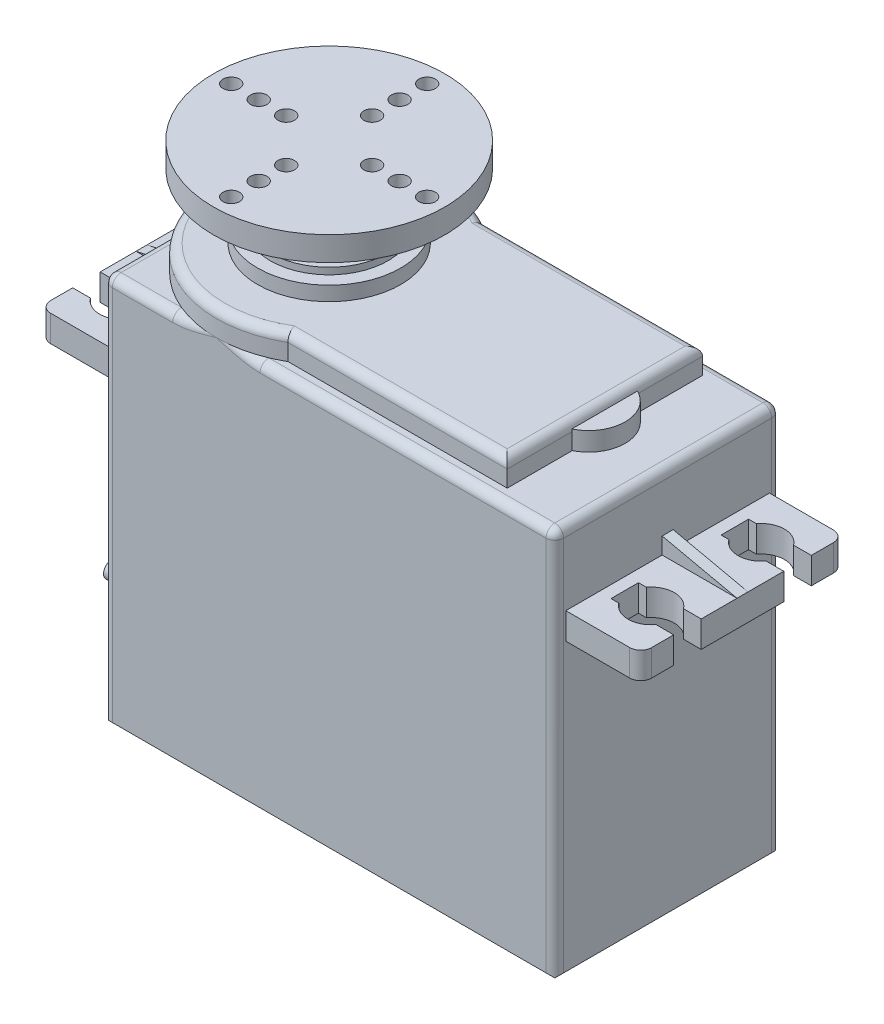
SolidWorks part; units mm, degrees
ref_plane "Front Plane" through (0, 0, 0) normal (0, 0, 1) x (1, 0, 0)
ref_plane "Top Plane" through (0, 0, 0) normal (0, 1, 0) x (1, 0, 0)
ref_plane "Right Plane" through (0, 0, 0) normal (1, 0, 0) x (0, 0, -1)
sketch "Sketch1" plane through (0, 0, 0) normal (0, 1, 0) x (1, 0, 0)
  line L1 (-20.5, 10.25) -> (20.5, 10.25)
  line L2 (-20.5, 10.25) -> (-20.5, -10.25)
  line L3 (-20.5, -10.25) -> (20.5, -10.25)
  line L4 (20.5, 10.25) -> (20.5, -10.25)
  line L5 (-20.5, 10.25) -> (20.5, -10.25) construction
  line L6 (-20.5, -10.25) -> (20.5, 10.25) construction
  point P0 (0, 0)
  dimension "D1" = 20.5
  dimension "D2" = 41
extrude "Boss-Extrude1" add sketch "Sketch1" along normal blind 37
chamfer "Chamfer1" distance 2 angle 45 4 edges at (-20.5, 0, 0) (0, 0, -10.25) (20.5, 0, 0) (0, 0, 10.25)
sketch "Sketch2" plane through (0, 37, 0) normal (0, 1, 0) x (1, 0, 0)
  line L0 (-20.5, 0) -> (20.5, 0) construction
  line L1 (-20.5, 10.25) -> (-20.5, -10.25) construction
  line L2 (20.5, -10.25) -> (20.5, 10.25) construction
  line L3 (20.5, 10.25) -> (-20.5, 10.25) construction
  line L4 (-5.122, 8.875) -> (14.8, 8.875)
  line L5 (14.8, 8.875) -> (14.8, -8.875)
  line L6 (14.8, -8.875) -> (-5.122, -8.875)
  arc A0 (-5.122, 8.875) -> (-5.122, -8.875) centre (-10.25, 0) ccw
  arc A1 (14.8, -2.9719) -> (14.8, 2.9719) centre (13.32, 0) ccw
  dimension "D1" = 17.75
  dimension "D2" = 6.64
  dimension "D3" = 1.48
  dimension "D4" = 5.7
extrude "Boss-Extrude2" add sketch "Sketch2" along normal blind 2.3 contours L0 A0 L6 L5 | A0 L0 L5 L4 | L0 L5 A1 | L5 L0 A1 region at (-2.3856, 37, -4.4911) region at (-2.3856, 37, 4.4911) region at (15.5569, 37, -1.1714) region at (15.5569, 37, 1.1714)
sketch "Sketch3" plane through (0, 39.3, 0) normal (0, 1, 0) x (1, 0, 0)
  line L3 (14.8, 8.875) -> (-5.122, 8.875)
  line L4 (14.8, -8.875) -> (14.8, 8.875)
  line L5 (-5.122, -8.875) -> (14.8, -8.875)
  line L7 (14.8, -2.9719) -> (14.8, 2.9719)
  arc A0 (14.8, -2.9719) -> (14.8, 2.9719) centre (13.32, 0) ccw construction
  arc A1 (-5.122, 8.875) -> (-5.122, -8.875) centre (-10.25, 0) ccw
  arc A3 (14.8, -2.9719) -> (14.8, 2.9719) centre (13.32, 0) ccw
  dimension "D1" = 0
extrude "Cut-Extrude2" cut sketch "Sketch3" against normal blind 0.6
sketch "Sketch4" plane through (0, 39.3, 0) normal (0, 1, 0) x (1, 0, 0)
  circle A0 centre (-10.25, 0) radius 6.5
  dimension "D1" = 13
extrude "Boss-Extrude3" add sketch "Sketch4" along normal blind 1.3
sketch "Sketch5" plane through (0, 40.6, 0) normal (0, 1, 0) x (1, 0, 0)
  circle A0 centre (-10.25, 0) radius 5.35
  dimension "D1" = 10.7
extrude "Boss-Extrude4" add sketch "Sketch5" along normal blind 0.6
sketch "Sketch6" plane through (0, 41.2, 0) normal (0, 1, 0) x (1, 0, 0)
  circle A0 centre (-10.25, 0) radius 3
  dimension "D1" = 6
extrude "Boss-Extrude5" add sketch "Sketch6" along normal blind 4
sketch "Sketch7" plane through (0, 45.2, 0) normal (0, 1, 0) x (1, 0, 0)
  circle A0 centre (-10.25, 0) radius 10.5
  dimension "D1" = 21
extrude "Boss-Extrude6" add sketch "Sketch7" along normal blind 2.2
sketch "Sketch8" plane through (0, 47.4, 0) normal (0, 1, 0) x (1, 0, 0)
  circle A0 centre (-14.15, 0) radius 0.75
  circle A1 centre (-16.65, 0) radius 0.75
  circle A2 centre (-19.15, 0) radius 0.75
  point P6 (-10.25, 0)
  dimension "D1" = 1.5
  dimension "D2" = 2.5
  dimension "D3" = 2.5
  dimension "D4" = 3.9
extrude "Cut-Extrude3" cut sketch "Sketch8" against normal up to next
pattern_circular "CirPattern1" count 4 over 360 about axis through (-10.25, 47.4, 0) along (0, -1, 0) of "Cut-Extrude3"
sketch "Sketch9" plane through (-20.5, 0, 0) normal (-1, 0, 0) x (0, 0, 1)
  line L1 (-3.5, 7.4) -> (3.5, 7.4)
  line L2 (-3.5, 7.4) -> (-3.5, 3.2)
  line L3 (-3.5, 3.2) -> (3.5, 3.2)
  line L4 (3.5, 7.4) -> (3.5, 3.2)
  line L5 (-3.5, 7.4) -> (3.5, 3.2) construction
  line L6 (-3.5, 3.2) -> (3.5, 7.4) construction
  point P0 (0, 5.3)
  dimension "D1" = 4.2
  dimension "D2" = 3.2
  dimension "D3" = 7
extrude "Boss-Extrude7" add sketch "Sketch9" along normal blind 1
sketch "Sketch10" plane through (-21.5, 0, 0) normal (-1, 0, 0) x (0, 0, 1)
  line L8 (3.15, 3.55) -> (3.15, 7.05)
  line L9 (3.15, 7.05) -> (-3.15, 7.05)
  line L10 (-3.15, 7.05) -> (-3.15, 3.55)
  line L11 (-3.15, 3.55) -> (3.15, 3.55)
  line L12 (3.15, 3.55) -> (3.15, 7.05)
  line L13 (3.15, 7.05) -> (-3.15, 7.05)
  line L14 (-3.15, 7.05) -> (-3.15, 3.55)
  line L15 (-3.15, 3.55) -> (3.15, 3.55)
  dimension "D1" = 0.35
extrude "Boss-Extrude8" add sketch "Sketch10" along normal blind 4 draft 5
sketch "Sketch11" plane through (-25.5, 0, 0) normal (-1, 0, 0) x (0, 0, 1)
  line L0 (-2.8, 3.9) -> (2.8, 3.9) construction
  circle A0 centre (0, 5.3) radius 0.75
  circle A1 centre (1.5, 5.3) radius 0.75
  circle A2 centre (-1.5, 5.3) radius 0.75
  dimension "D1" = 1.5
  dimension "D2" = 1.4
extrude "Boss-Extrude10" add sketch "Sketch11" along normal blind 3 separate body contours A2 | A0 | A1 region at (-25.5, 5.3, 0) region at (-25.5, 5.3, -1.5) region at (-25.5, 5.3, 1.5)
fillet "Fillet1" radius 0.8 4 edges at (20.5, 19.5, 10.25) (20.5, 19.5, -10.25) (-20.5, 19.5, -10.25) (-20.5, 19.5, 10.25)
fillet "Fillet2" radius 0.8 4 edges at (4.839, 39.3, -8.875) (14.8, 39.3, 0) (4.839, 39.3, 8.875) (-20.5, 39.3, 0)
fillet "Fillet3" radius 0.8 11 edges at (-14.975, 37, 10.25) (-20.2657, 37, 10.0157) (-20.5, 37, 4.725) (-20.5, 37, -4.725) (-20.2657, 37, -10.0157) (-14.975, 37, -10.25) (4.725, 37, -10.25) (20.2657, 37, -10.0157) (20.5, 37, 0) (20.2657, 37, 10.0157) (4.725, 37, 10.25)
sketch "Sketch12" plane through (-20.5, 0, 0) normal (-1, 0, 0) x (0, 0, 1)
  line L1 (9.25, 30.4) -> (-9.25, 30.4)
  line L2 (9.25, 30.4) -> (9.25, 28)
  line L3 (9.25, 28) -> (-9.25, 28)
  line L4 (-9.25, 30.4) -> (-9.25, 28)
  line L5 (9.25, 30.4) -> (-9.25, 28) construction
  line L6 (9.25, 28) -> (-9.25, 30.4) construction
  line L7 (9.45, 36.2) -> (3.9699, 36.2) construction
  line L8 (-10.25, 2) -> (-10.25, 36.2) construction
  point P0 (0, 29.2)
  dimension "D1" = 18.5
  dimension "D2" = 2.4
  dimension "D3" = 5.8
  dimension "D4" = 1
extrude "Boss-Extrude11" add sketch "Sketch12" along normal blind 6.8
fillet "Fillet4" radius 1 2 edges at (-27.3, 29.2, -9.25) (-27.3, 29.2, 9.25)
sketch "Sketch13" plane through (0, 30.4, 0) normal (0, 1, 0) x (1, 0, 0)
  line L0 (-27.3, 0) -> (-20.75, 0) construction
  line L1 (-27.3, -8.25) -> (-27.3, 8.25) construction
  line L2 (-22.3125, 3.75) -> (-21.6, 3.75)
  line L3 (-27.3, 6.25) -> (-25.6875, 6.25)
  line L4 (-27.3, 6.25) -> (-27.3, 3.75)
  line L5 (-27.3, 3.75) -> (-25.6875, 3.75)
  line L6 (-21.6, 6.25) -> (-21.6, 3.75)
  line L7 (-27.3, 6.25) -> (-21.6, 3.75) construction
  line L8 (-27.3, 3.75) -> (-21.6, 6.25) construction
  line L9 (-22.3125, 6.25) -> (-21.6, 6.25)
  circle A0 centre (-10.25, 0) radius 10.5 construction
  arc A1 (-25.6875, 3.75) -> (-22.3125, 3.75) centre (-24, 5) ccw
  arc A2 (-22.3125, 6.25) -> (-25.6875, 6.25) centre (-24, 5) ccw
  point P7 (-24.45, 5)
  dimension "D3" = 4.2
  dimension "D1" = 2.5
  dimension "D2" = 5.7
  dimension "D4" = 3.3
  dimension "D5" = 5
extrude "Cut-Extrude4" cut sketch "Sketch13" against normal blind 6.8
mirror "Mirror1" about plane through (0, 0, 0) normal (0, 0, 1) of "Cut-Extrude4"
sketch "Sketch14" plane through (0, 0, 0) normal (0, 0, 1) x (1, 0, 0)
  line L0 (-27.3, 30.4) -> (-20.5, 30.4)
  line L1 (-20.5, 30.4) -> (-20.5, 31.9)
  line L2 (-20.5, 2) -> (-20.5, 36.2) construction
  line L3 (-20.5, 31.9) -> (-27.3, 30.4)
  dimension "D1" = 1.5
extrude "Boss-Extrude12" add sketch "Sketch14" along normal mid plane 1
ref_plane "Plane1" through (0, 0, 0) normal (-1, 0, 0) x (0, 0, 1)
mirror "Mirror2" about plane through (0, 0, 0) normal (-1, 0, 0) of "Boss-Extrude12", "Mirror1", "Cut-Extrude4", "Fillet4", "Boss-Extrude11"
